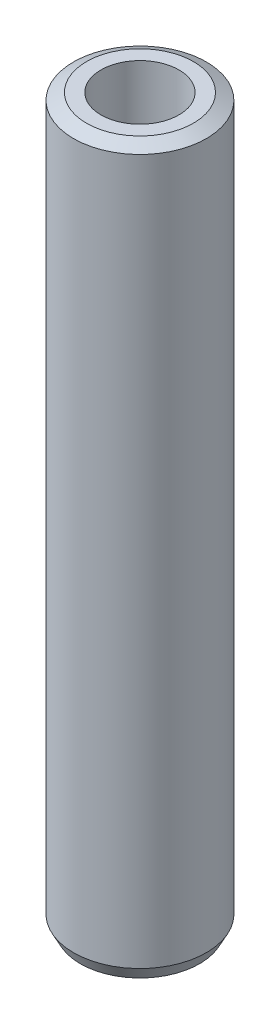
SolidWorks part; units mm, degrees
ref_plane "Front Plane" through (0, 0, 0) normal (0, 0, 1) x (1, 0, 0)
ref_plane "Top Plane" through (0, 0, 0) normal (0, 1, 0) x (1, 0, 0)
ref_plane "Right Plane" through (0, 0, 0) normal (1, 0, 0) x (0, 0, -1)
sketch "Sketch1" plane through (0, 0, 0) normal (0, 1, 0) x (1, 0, 0)
  circle A0 centre (0, 0) radius 55
  dimension "SHAFT_OD" = 110
extrude "Boss-Extrude1" add sketch "Sketch1" along normal blind 600
sketch "Sketch2" plane through (0, 0, 0) normal (0, 1, 0) x (1, 0, 0)
  circle A0 centre (0, 0) radius 32.2938
  dimension "BORE_D" = 64.5876
extrude "Cut-Extrude1" cut sketch "Sketch2" along normal through all
chamfer "Chamfer1" distance 5.6254 angle 62.418 2 edges at (0, 600, 55) (0, 0, 55) first distance on face at (0, 600, 55) first distance on face at (0, 0, 32.2938)
